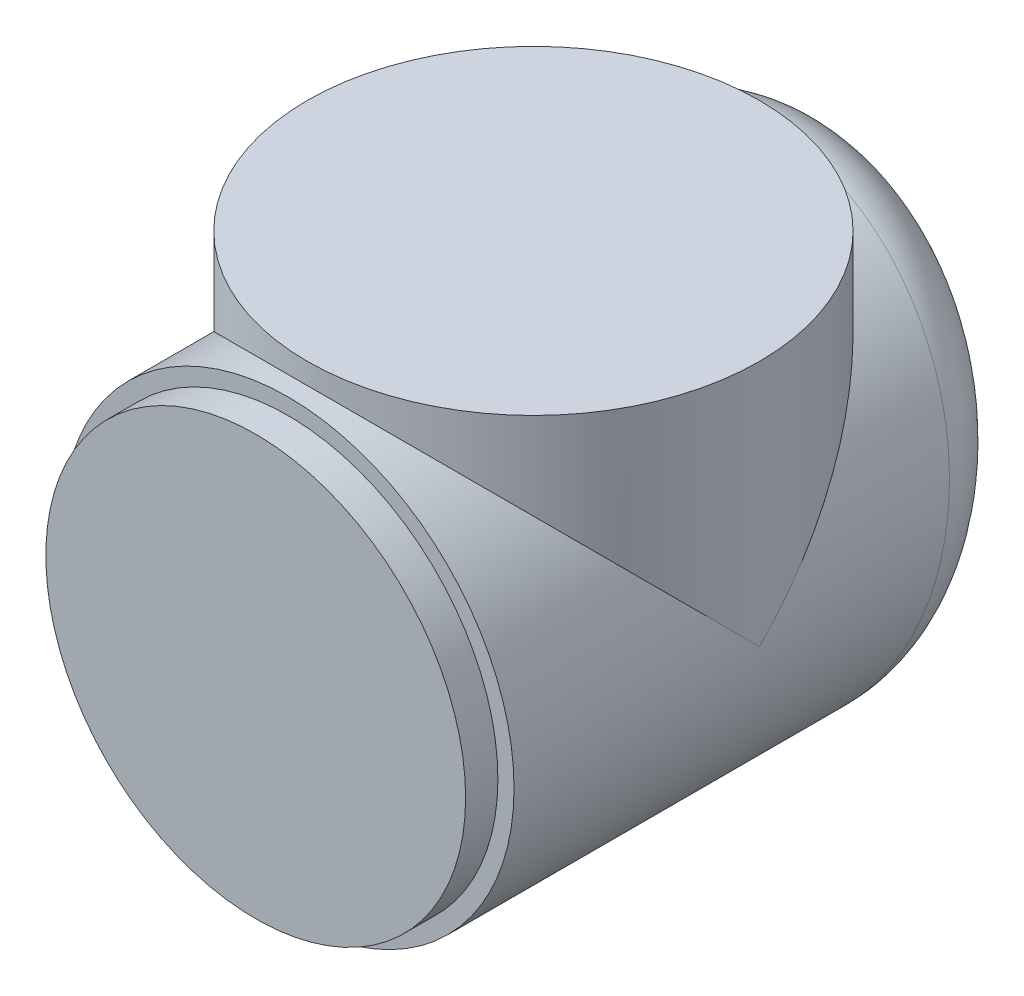
SolidWorks part; units mm, degrees
ref_plane "Front Plane" through (0, 0, 0) normal (0, 0, 1) x (1, 0, 0)
ref_plane "Top Plane" through (0, 0, 0) normal (0, 1, 0) x (1, 0, 0)
ref_plane "Right Plane" through (0, 0, 0) normal (1, 0, 0) x (0, 0, -1)
sketch "Sketch1" plane through (0, 0, 0) normal (0, 0, 1) x (1, 0, 0)
  circle A0 centre (0, 0) radius 35
  dimension "D1" = 70
extrude "Boss-Extrude1" add sketch "Sketch1" along normal blind 43 and the other way blind 49.1
sketch "Sketch2" plane through (0, 0, 0) normal (1, 0, 0) x (0, 0, -1)
  line L0 (49.1, 35) -> (49.1, -35)
  line L1 (49.1, -35) -> (29.1, -35)
  line L2 (-43, -35) -> (49.1, -35) construction
  line L3 (29.1, -35) -> (49.1, 35)
  dimension "D1" = 20
extrude "Cut-Extrude1" cut sketch "Sketch2" against normal through all both and the other way through all
fillet "Fillet1" radius 10 1 edges at (0, -35, -29.1)
sketch "Sketch3" plane through (0, 0, 0) normal (0, 1, 0) x (1, 0, 0)
  circle A0 centre (0, 0) radius 35
  dimension "D1" = 70
extrude "Boss-Extrude2" add sketch "Sketch3" along normal blind 38.25
sketch "Sketch4" plane through (0, 0, 43) normal (0, 0, 1) x (1, 0, 0)
  circle A0 centre (0, 0) radius 35
  circle A1 centre (0, 0) radius 32.5
  dimension "D1" = 70
  dimension "D2" = 65
extrude "Cut-Extrude2" cut sketch "Sketch4" against normal blind 5
ref_plane "Plane1" through (0, 0, 0) normal (0, 0, 1) x (1, 0, 0)
sketch "Sketch5" plane through (0, 0, 43) normal (0, 0, 1) x (1, 0, 0)
  line L0 (-32.5, 0) -> (32.5, 0) construction
  line L1 (0, 32.5) -> (0, -32.5) construction
  circle A0 centre (0, 0) radius 32.5 construction
  point P7 (0, 0)
